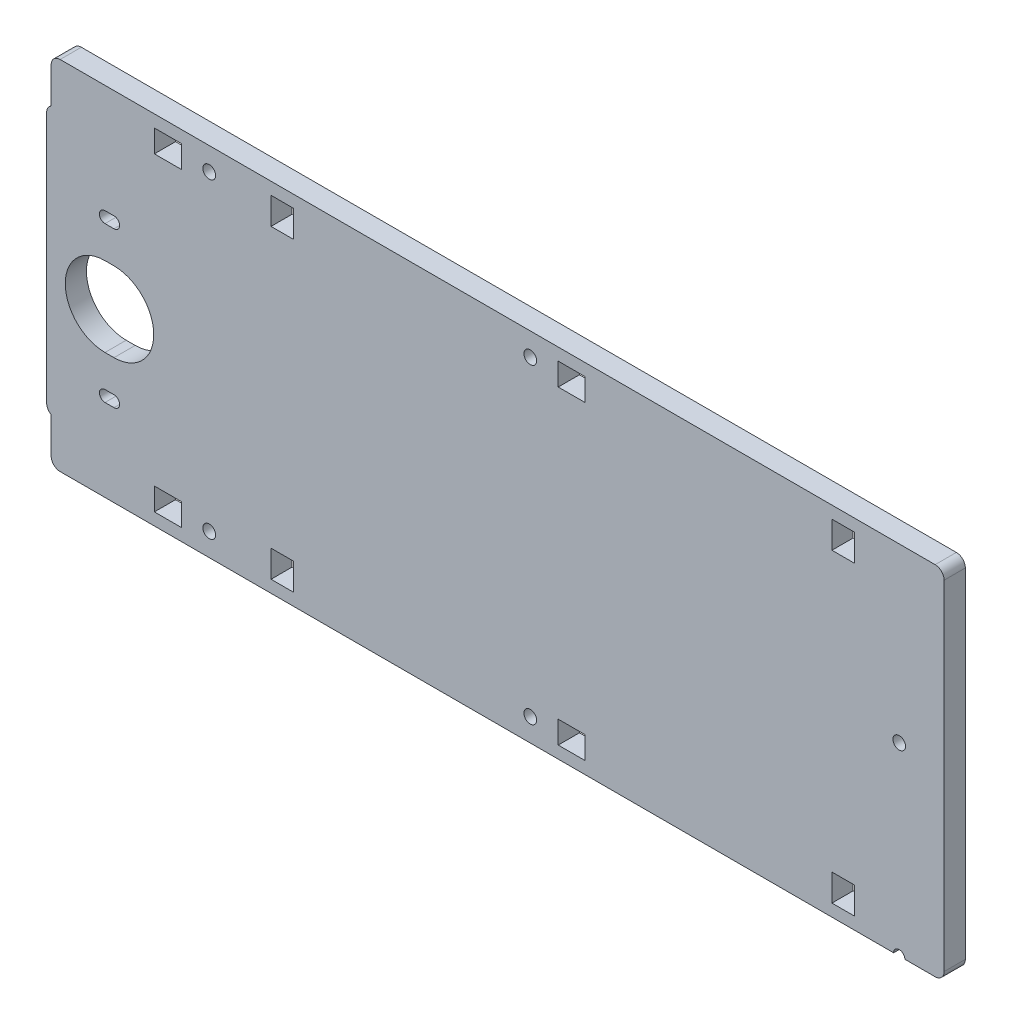
SolidWorks part; units mm, degrees
material "Acrylic (Medium-high impact)"
ref_plane "Front Plane" through (0, 0, 0) normal (0, 0, 1) x (1, 0, 0)
ref_plane "Top Plane" through (0, 0, 0) normal (0, 1, 0) x (1, 0, 0)
ref_plane "Right Plane" through (0, 0, 0) normal (1, 0, 0) x (0, 0, -1)
sketch "Sketch1" plane through (0, 0, 0) normal (0, 0, 1) x (1, 0, 0)
  line L1 (0, 0) -> (254, 0)
  line L2 (0, 0) -> (0, 101.0158)
  line L3 (0, 101.0158) -> (254, 101.0158)
  line L4 (254, 0) -> (254, 101.0158)
  line L5 (228.6, 97.5614) -> (222.25, 97.5614)
  line L6 (228.6, 97.5614) -> (228.6, 89.9414)
  line L7 (228.6, 89.9414) -> (222.25, 89.9414)
  line L8 (222.25, 97.5614) -> (222.25, 89.9414)
  line L9 (63.5, 97.5614) -> (69.85, 97.5614)
  line L10 (63.5, 97.5614) -> (63.5, 89.9414)
  line L11 (63.5, 89.9414) -> (69.85, 89.9414)
  line L12 (69.85, 97.5614) -> (69.85, 89.9414)
  line L13 (228.6, 3.4544) -> (222.25, 3.4544)
  line L14 (228.6, 3.4544) -> (228.6, 11.0744)
  line L15 (228.6, 11.0744) -> (222.25, 11.0744)
  line L16 (222.25, 3.4544) -> (222.25, 11.0744)
  line L17 (69.85, 3.4544) -> (63.5, 3.4544)
  line L18 (69.85, 3.4544) -> (69.85, 11.0744)
  line L19 (69.85, 11.0744) -> (63.5, 11.0744)
  line L20 (63.5, 3.4544) -> (63.5, 11.0744)
  dimension "D1" = 254
  dimension "D2" = 3.4544
  dimension "D3" = 7.62
  dimension "D4" = 6.35
  dimension "D5" = 25.4
  dimension "D6" = 165.1
  dimension "D7" = 3.4544
  dimension "D8" = 78.867
extrude "Boss-Extrude1" add sketch "Sketch1" along normal blind 6
sketch "Sketch2" plane through (0, 0, 6) normal (0, 0, 1) x (1, 0, 0)
  line L0 (0, 50.5079) -> (254, 50.5079) construction
  line L1 (0, 101.0158) -> (0, 0) construction
  line L2 (254, 0) -> (254, 101.0158) construction
  line L3 (16.51, 68.7198) -> (19.05, 68.7198) construction
  line L4 (17.78, 46.7995) -> (17.78, 68.7198) construction
  line L5 (17.78, 46.7995) -> (17.78, 24.8792) construction
  line L6 (17.78, 24.8792) -> (39.7003, 46.7995) construction
  line L7 (39.7003, 46.7995) -> (17.78, 68.7198) construction
  line L8 (17.78, 46.7995) -> (39.7003, 46.7995) construction
  line L9 (0, 40.5511) -> (254, 40.5511) construction
  line L10 (16.51, 70.3073) -> (19.05, 70.3073)
  line L11 (16.51, 67.1323) -> (19.05, 67.1323)
  line L12 (16.51, 24.8792) -> (19.05, 24.8792) construction
  line L13 (16.51, 26.4667) -> (19.05, 26.4667)
  line L14 (16.51, 23.2917) -> (19.05, 23.2917)
  line L15 (16.51, 46.7995) -> (19.05, 46.7995) construction
  line L16 (16.51, 58.0495) -> (19.05, 58.0495)
  line L17 (16.51, 35.5495) -> (19.05, 35.5495)
  circle A0 centre (17.78, 46.7995) radius 11.25 construction
  circle A1 centre (17.78, 68.7198) radius 1.5875 construction
  circle A2 centre (17.78, 24.8792) radius 1.5875 construction
  circle A3 centre (241.3, 52.2605) radius 1.778
  arc A4 (16.51, 70.3073) -> (16.51, 67.1323) centre (16.51, 68.7198) ccw
  arc A5 (19.05, 67.1323) -> (19.05, 70.3073) centre (19.05, 68.7198) ccw
  arc A6 (16.51, 26.4667) -> (16.51, 23.2917) centre (16.51, 24.8792) ccw
  arc A7 (19.05, 23.2917) -> (19.05, 26.4667) centre (19.05, 24.8792) ccw
  arc A8 (16.51, 58.0495) -> (16.51, 35.5495) centre (16.51, 46.7995) ccw
  arc A9 (19.05, 35.5495) -> (19.05, 58.0495) centre (19.05, 46.7995) ccw
  point P19 (17.78, 68.7198)
  point P24 (17.78, 24.8792)
  point P33 (17.78, 46.7995)
  dimension "D4" = 3.175
  dimension "D5" = 22.5
  dimension "D6" = 3.556
  dimension "D1" = 9.9568
  dimension "D2" = 12.7
  dimension "D3" = 31
  dimension "D7" = 1.7526
  dimension "D8" = 17.78
  dimension "D9" = 6.2484
  dimension "D10" = 2.54
  dimension "D11" = 2.54
extrude "Cut-Extrude1" cut sketch "Sketch2" against normal through all
sketch "Sketch3" plane through (0, 0, 6) normal (0, 0, 1) x (1, 0, 0)
  line L0 (38.1, 91.5614) -> (30.48, 91.5614) construction
  line L1 (30.48, 97.5614) -> (38.1, 97.5614)
  line L2 (30.48, 97.5614) -> (30.48, 91.5614)
  line L3 (30.48, 91.5614) -> (38.1, 91.5614)
  line L4 (38.1, 97.5614) -> (38.1, 91.5614)
  line L5 (144.78, 91.5614) -> (38.1, 91.5614) construction
  line L6 (152.4, 3.4544) -> (144.78, 3.4544) construction
  line L7 (144.78, 97.5614) -> (152.4, 97.5614)
  line L8 (144.78, 97.5614) -> (144.78, 91.5614)
  line L9 (144.78, 91.5614) -> (152.4, 91.5614)
  line L10 (152.4, 97.5614) -> (152.4, 91.5614)
  line L11 (144.78, 9.4544) -> (152.4, 9.4544)
  line L12 (144.78, 9.4544) -> (144.78, 3.4544)
  line L13 (144.78, 3.4544) -> (152.4, 3.4544)
  line L14 (152.4, 9.4544) -> (152.4, 3.4544)
  line L15 (38.1, 97.5614) -> (38.1, 91.5614) construction
  line L16 (30.48, 9.4544) -> (38.1, 9.4544)
  line L17 (30.48, 9.4544) -> (30.48, 3.4544)
  line L18 (30.48, 3.4544) -> (38.1, 3.4544)
  line L19 (38.1, 9.4544) -> (38.1, 3.4544)
  line L20 (152.4, 9.4544) -> (152.4, 3.4544) construction
extrude "Cut-Extrude2" cut sketch "Sketch3" against normal through all
sketch "Sketch4" plane through (0, 0, 6) normal (0, 0, 1) x (1, 0, 0)
  line L0 (38.1, 97.5614) -> (30.48, 97.5614) construction
  line L1 (30.48, 91.5614) -> (38.1, 91.5614)
  line L2 (30.48, 91.5614) -> (30.48, 91.2114)
  line L3 (30.48, 91.2114) -> (38.1, 91.2114)
  line L4 (38.1, 91.5614) -> (38.1, 91.2114)
  line L5 (30.48, 9.4544) -> (38.1, 9.4544)
  line L6 (30.48, 9.4544) -> (30.48, 9.8044)
  line L7 (30.48, 9.8044) -> (38.1, 9.8044)
  line L8 (38.1, 9.4544) -> (38.1, 9.8044)
  line L9 (152.4, 91.5614) -> (144.78, 91.5614)
  line L10 (152.4, 91.5614) -> (152.4, 91.2114)
  line L11 (152.4, 91.2114) -> (144.78, 91.2114)
  line L12 (144.78, 91.5614) -> (144.78, 91.2114)
  line L13 (152.4, 9.4544) -> (144.78, 9.4544)
  line L14 (152.4, 9.4544) -> (152.4, 9.8044)
  line L15 (152.4, 9.8044) -> (144.78, 9.8044)
  line L16 (144.78, 9.4544) -> (144.78, 9.8044)
  line L17 (38.1, 3.4544) -> (38.1, 9.4544) construction
  dimension "D1" = 6.35
extrude "Cut-Extrude3" cut sketch "Sketch4" against normal up to next
sketch "Sketch8" plane through (0, 0, 6) normal (0, 0, 1) x (1, 0, 0)
  line L1 (0, 101.0158) -> (1.27, 101.0158)
  line L2 (0, 101.0158) -> (0, 88.3158)
  line L3 (0, 88.3158) -> (1.27, 88.3158)
  line L4 (1.27, 101.0158) -> (1.27, 88.3158)
  line L5 (0, 0) -> (1.27, 0)
  line L6 (0, 0) -> (0, 12.7)
  line L7 (0, 12.7) -> (1.27, 12.7)
  line L8 (1.27, 0) -> (1.27, 12.7)
  dimension "D1" = 1.27
  dimension "D2" = 12.7
extrude "Cut-Extrude6" cut sketch "Sketch8" against normal through all
fillet "Fillet1" radius 2.54 6 edges at (254, 0, 3) (254, 101.0158, 3) (0, 88.3158, 3) (0, 12.7, 3) (1.27, 0, 3) (1.27, 101.0158, 3)
sketch "Sketch6" plane through (0, 0, 6) normal (0, 0, 1) x (1, 0, 0)
  line L0 (135.3058, 94.5614) -> (138.43, 94.5614) construction
  line L1 (138.43, 6.4544) -> (135.3058, 6.4544) construction
  line L2 (44.45, 94.5614) -> (47.5742, 94.5614) construction
  line L3 (44.45, 6.4544) -> (47.5742, 6.4544) construction
  circle A0 centre (46.0121, 6.4544) radius 1.8034
  circle A1 centre (136.8679, 6.4544) radius 1.8034
  circle A2 centre (46.0121, 94.5614) radius 1.8034
  circle A3 centre (136.8679, 94.5614) radius 1.8034
  dimension "D1" = 3.6068
extrude "Cut-Extrude4" cut sketch "Sketch6" against normal through all
sketch "Sketch7" plane through (0, 0, 6) normal (0, 0, 1) x (1, 0, 0)
  line L0 (3.81, 0) -> (251.46, 0) construction
  line L1 (254, 2.54) -> (254, 98.4758) construction
  circle A0 centre (241.3, 0) radius 1.5875
  dimension "D2" = 3.175
  dimension "D1" = 12.7
extrude "Cut-Extrude5" cut sketch "Sketch7" against normal through all
